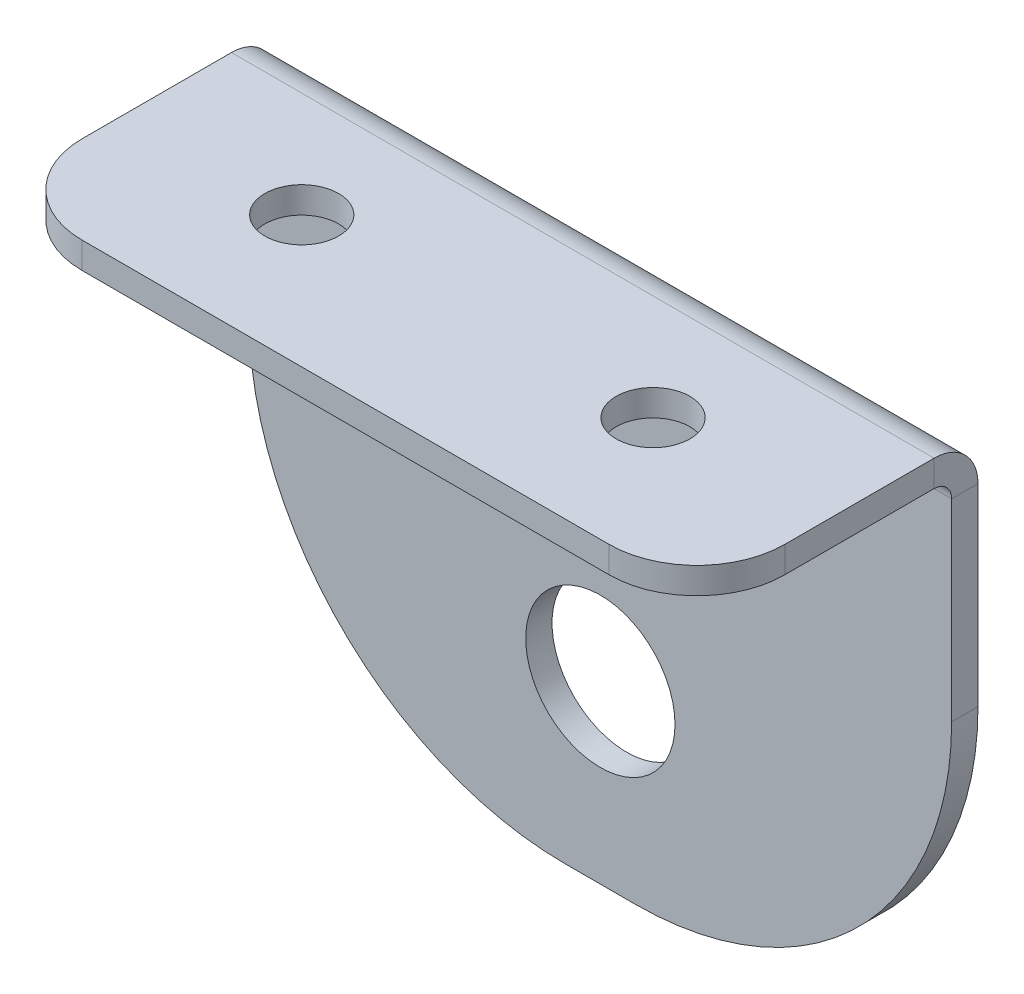
SolidWorks part; units mm, degrees
note: The reader was unsure of these and kept them because the rebuilt part matched: flange length of "边线-法兰1".
material "1023 碳钢板 (SS)"
ref_plane "前视基准面" through (0, 0, 0) normal (0, 0, 1) x (1, 0, 0)
ref_plane "上视基准面" through (0, 0, 0) normal (0, 1, 0) x (1, 0, 0)
ref_plane "右视基准面" through (0, 0, 0) normal (1, 0, 0) x (0, 0, -1)
sketch "草图1" plane through (0, 0, 0) normal (0, 0, 1) x (1, 0, 0)
  line L0 (0, 0) -> (20568.7415, 0) construction
  line L1 (0, 0) -> (0, 20568.7415) construction
  line L3 (-20, 21.5) -> (20, 21.5)
  line L4 (-20, 21.5) -> (-20, 8)
  line L5 (-2, -10) -> (2, -10)
  line L6 (20, 21.5) -> (20, 8)
  circle A0 centre (0, 0) radius 4.25
  arc A4 (2, -10) -> (20, 8) centre (2, 8) ccw
  arc A5 (-20, 8) -> (-2, -10) centre (-2, 8) ccw
  dimension "D4" = 8.5
  dimension "D7" = 18
  dimension "D1" = 40
  dimension "D2" = 10
  dimension "D3" = 21.5
base flange "基体-法兰1" sketch "草图1" thickness 1.5 reverse thickness direction no parameters "D1"=1
edge flange "边线-法兰1" sketch "草图8" flange angle 90 flange length 16 flange position material inside bend radius 1 thickness 1.5 relief rectangular parameters "D6"=10
sketch "草图8" plane through (0, 21.5, 0) normal (0, 1, 0) x (-1, 0, 0)
  line L0 (-20, 0) -> (20, 0) construction
  line L1 (-20, 0) -> (20, 0)
  line L2 (-20, 0) -> (-20, 9.5)
  line L3 (-15, 14.5) -> (15, 14.5)
  line L4 (20, 9.5) -> (20, 0)
  line L5 (0, 0) -> (0, 50000) construction
  arc A0 (15, 14.5) -> (20, 9.5) centre (15, 9.5) cw
  arc A1 (-20, 9.5) -> (-15, 14.5) centre (-15, 9.5) cw
  circle A2 centre (-10, 7) radius 2.1
  circle A3 centre (10, 7) radius 2.1
  point P13 (0, 0)
  dimension "D1" = 5
  dimension "D2" = 4.2
  dimension "D3" = 7
  dimension "D4" = 10
  dimension "D5" = 14.5
bend "边线折弯1" bend radius 1 bend angle 90 parameters "D5"=1
sketch "折弯-线1" [suppressed] plane through (0, 0, 0) normal (0, 1, 0) x (1, 0, 0)
sketch "边界框1" [suppressed] plane through (0, 0, 0) normal (0, 1, 0) x (1, 0, 0)
sheet metal parameters "钣金6" thickness 1.5 parameters "D1"=2
flat pattern "平板型式6" [suppressed]
sketch "折弯-线2" plane through (0, 0, 0) normal (0, 1, 0) x (1, 0, 0)
sketch3d "边界框2" [suppressed]
  line L0 (37, -3, 0) -> (37, 38, 0) construction
  line L1 (-3, -3, 0) -> (-3, 38, 0) construction
  line L2 (37, -3, 0) -> (-3, -3, 0) construction
  line L3 (37, 38, 0) -> (-3, 38, 0) construction
sheet metal parameters "钣金7" thickness 1.5 parameters "D1"=2
flat pattern "平板型式6"
sketch "折弯-线2" plane through (0, 0, 0) normal (0, 0, 1) x (1, 0, 0)
  line L0 (20, 20.089) -> (-20, 20.089) construction
  line L1 (20, 20.089) -> (-20, 20.089) construction
sketch3d "边界框2" [suppressed]
  line L0 (37, -3, 0) -> (37, 52.1781, 0) construction
  line L1 (-3, -3, 0) -> (-3, 52.1781, 0) construction
  line L2 (37, -3, 0) -> (-3, -3, 0) construction
  line L3 (37, 52.1781, 0) -> (-3, 52.1781, 0) construction
bend of the flat pattern "展开-<边线折弯1>1"
